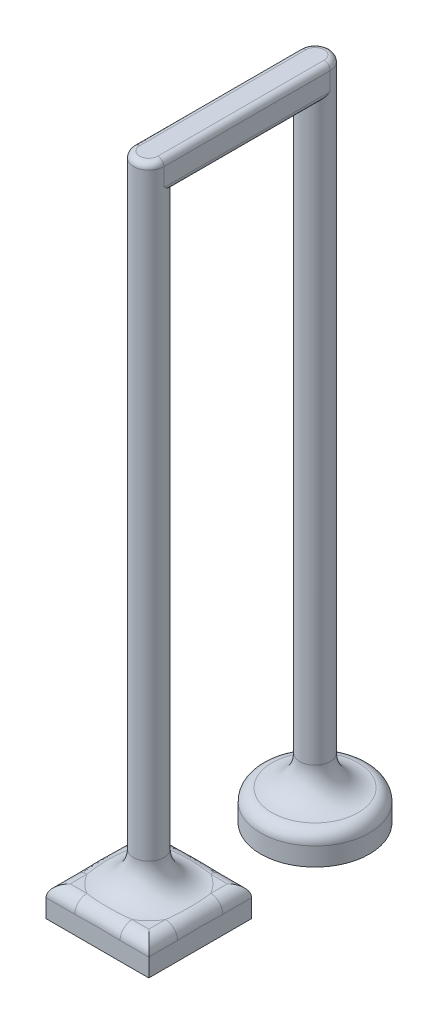
SolidWorks part; units mm, degrees
ref_plane "Front Plane" through (0, 0, 0) normal (0, 0, 1) x (1, 0, 0)
ref_plane "Top Plane" through (0, 0, 0) normal (0, 1, 0) x (1, 0, 0)
ref_plane "Right Plane" through (0, 0, 0) normal (1, 0, 0) x (0, 0, -1)
sketch "Sketch1" plane through (0, 0, 0) normal (0, 1, 0) x (1, 0, 0)
  line L1 (2.5, -13.75) -> (-2.5, -13.75)
  line L2 (2.5, -13.75) -> (2.5, 13.75)
  line L3 (2.5, 13.75) -> (-2.5, 13.75)
  line L4 (-2.5, -13.75) -> (-2.5, 13.75)
  line L5 (2.5, -13.75) -> (-2.5, 13.75) construction
  line L6 (2.5, 13.75) -> (-2.5, -13.75) construction
  circle A0 centre (0, -13.75) radius 2.5
  circle A1 centre (0, 13.75) radius 2.5
  point P0 (0, 0)
  dimension "D1" = 5
  dimension "D2" = 27.5
extrude "Boss-Extrude1" add sketch "Sketch1" along normal blind 5 contours L3 A1 | L3 A1 | A1 L4 A0 L2 | L1 A0 | L1 A0 region at (0, 0, 14.811) region at (0, 0, 0) region at (0, 0, 12.689) region at (0, 0, -12.689) region at (0, 0, -14.811)
extrude "Boss-Extrude2" add sketch "Sketch1<4>" against normal blind 100 contours L3 A1 | L3 A1 | L1 A0 | L1 A0 region at (0, 0, 14.811) region at (0, 0, 12.689) region at (0, 0, -12.689) region at (0, 0, -14.811)
sketch "Sketch1<4>" plane through (0, 0, 0) normal (0, 1, 0) x (1, 0, 0) same geometry as "Sketch1"
sketch "Sketch2" plane through (0, -100, 0) normal (0, -1, 0) x (1, 0, 0)
  line L1 (8.5, 22.25) -> (-8.5, 22.25)
  line L2 (8.5, 22.25) -> (8.5, 5.25)
  line L3 (8.5, 5.25) -> (-8.5, 5.25)
  line L4 (-8.5, 22.25) -> (-8.5, 5.25)
  line L5 (8.5, 22.25) -> (-8.5, 5.25) construction
  line L6 (8.5, 5.25) -> (-8.5, 22.25) construction
  circle A0 centre (0, -13.75) radius 9
  point P3 (0, 13.75)
  dimension "D1" = 18
  dimension "D2" = 17
  dimension "D3" = 17
extrude "Boss-Extrude3" add sketch "Sketch2" along normal blind 5
fillet "Fillet1" radius 5 2 edges at (0, -100, -11.25) (0, -100, 16.25)
fillet "Fillet2" radius 2 4 edges at (-8.5, -100, 13.75) (0, -100, 22.25) (0, -100, 5.25) (8.5, -100, 13.75)
fillet "Fillet3" radius 2 1 edges at (0, -100, -22.75)
fillet "Fillet4" radius 1 6 edges at (0, 5, 16.25) (-2.5, 5, 0) (0, 5, -16.25) (2.5, 5, 0) (-2.5, 0, 0) (2.5, 0, 0)
